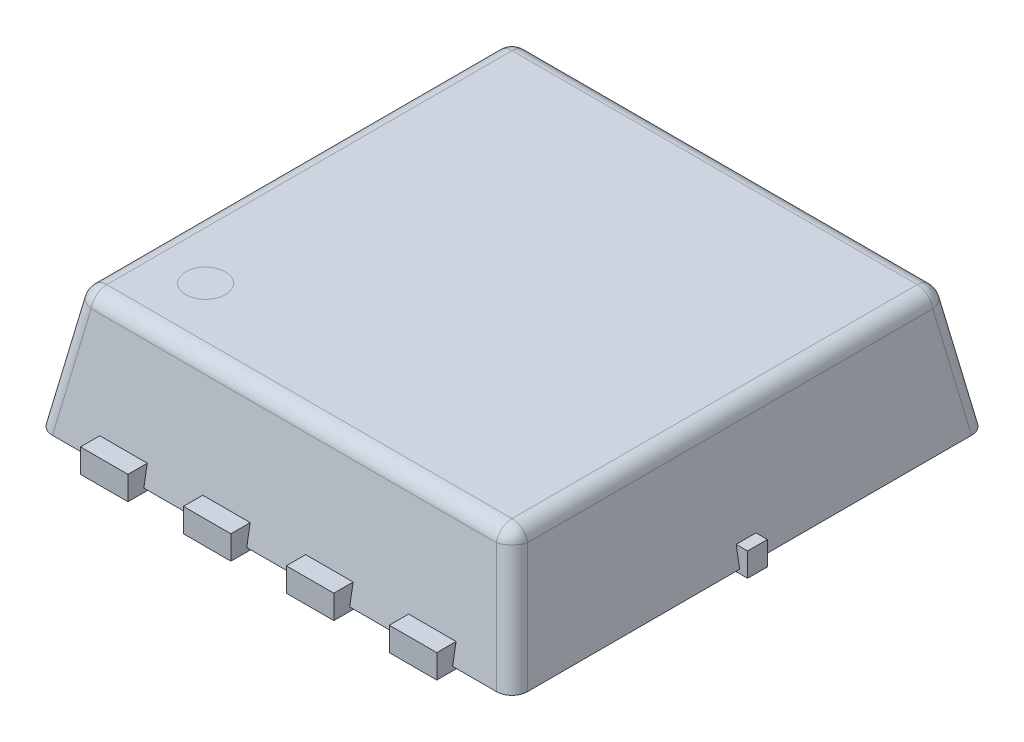
SolidWorks part; units mm, degrees
note: The reader was unsure of these and kept them because the rebuilt part matched: shared geometry of "Эскиз2<2>", "Эскиз3<2>".
ref_plane "Спереди" through (0, 0, 0) normal (0, 0, 1) x (1, 0, 0)
ref_plane "Сверху" through (0, 0, 0) normal (0, 1, 0) x (1, 0, 0)
ref_plane "Справа" through (0, 0, 0) normal (1, 0, 0) x (0, 0, -1)
sketch "Эскиз1" plane through (0, 0, 0) normal (0, 1, 0) x (1, 0, 0)
  line L1 (-1.5, -1.5) -> (1.5, -1.5)
  line L2 (-1.5, -1.5) -> (-1.5, 1.5)
  line L3 (-1.5, 1.5) -> (1.5, 1.5)
  line L4 (1.5, -1.5) -> (1.5, 1.5)
  line L5 (-1.5, -1.5) -> (1.5, 1.5) construction
  line L6 (-1.5, 1.5) -> (1.5, -1.5) construction
  point P0 (0, 0)
  dimension "D1" = 3
  dimension "D2" = 3
extrude "Бобышка-Вытянуть1" add sketch "Эскиз1" along normal blind 0.775 draft 10 from offset 0.025
fillet "Скругление1" radius 0.1 8 edges at (1.4317, 0.4125, -1.4317) (-1.4317, 0.4125, -1.4317) (-1.3633, 0.8, 0) (0, 0.8, -1.3633) (1.3633, 0.8, 0) (1.4317, 0.4125, 1.4317) (0, 0.8, 1.3633) (-1.4317, 0.4125, 1.4317)
sketch "Эскиз2" plane through (0, 0, 0) normal (0, 1, 0) x (1, 0, 0)
  line L0 (0, 0) -> (0, -1.5) construction
  line L1 (-0.975, 1.8089) -> (-0.975, -1.8739) construction
  line L2 (-0.475, -1.6) -> (-0.175, -1.6)
  line L3 (-1.125, -1.2) -> (-0.825, -1.2)
  line L4 (-1.125, -1.2) -> (-1.125, -1.6)
  line L5 (-1.125, -1.6) -> (-0.825, -1.6)
  line L6 (-0.825, -1.2) -> (-0.825, -1.6)
  line L7 (-1.125, -1.2) -> (-0.825, -1.6) construction
  line L8 (-1.125, -1.6) -> (-0.825, -1.2) construction
  line L9 (-0.475, -1.2) -> (-0.475, -1.6)
  line L10 (-0.475, -1.2) -> (-0.175, -1.2)
  line L11 (-0.175, -1.2) -> (-0.175, -1.6)
  line L12 (0.175, -1.6) -> (0.475, -1.6)
  line L13 (0.175, -1.2) -> (0.175, -1.6)
  line L14 (0.175, -1.2) -> (0.475, -1.2)
  line L15 (0.475, -1.2) -> (0.475, -1.6)
  line L16 (0.825, -1.6) -> (1.125, -1.6)
  line L17 (0.825, -1.2) -> (0.825, -1.6)
  line L18 (0.825, -1.2) -> (1.125, -1.2)
  line L19 (1.125, -1.2) -> (1.125, -1.6)
  line L20 (-0.825, -1.6) -> (1.125, -1.6) construction
  line L21 (-1.4015, -1.5) -> (1.4015, -1.5) construction
  line L22 (-0.175, 1.3) -> (-0.175, 1.6)
  line L23 (-1.125, 1.3) -> (-0.825, 1.3) construction
  line L24 (-1.125, 1.3) -> (-1.125, 1.6)
  line L25 (-1.125, 1.6) -> (-0.825, 1.6)
  line L26 (-0.825, 1.3) -> (-0.825, 1.6)
  line L27 (-1.125, 1.3) -> (-0.825, 1.6) construction
  line L28 (-1.125, 1.6) -> (-0.825, 1.3) construction
  line L29 (-0.475, 1.3) -> (-0.475, 1.6)
  line L30 (-0.475, 1.6) -> (-0.175, 1.6)
  line L31 (0.475, 1.3) -> (0.475, 1.6)
  line L32 (0.175, 1.3) -> (0.175, 1.6)
  line L33 (0.175, 1.6) -> (0.475, 1.6)
  line L34 (1.125, 1.3) -> (1.125, 1.6)
  line L35 (0.825, 1.3) -> (0.825, 1.6)
  line L36 (0.825, 1.6) -> (1.125, 1.6)
  line L37 (-0.825, 1.6) -> (1.125, 1.6) construction
  line L38 (-1.175, 1.3) -> (-1.175, 1.17)
  line L39 (-1.125, 1.3) -> (-1.175, 1.3) construction
  line L40 (-0.775, 1.3) -> (-0.775, 1.17)
  line L41 (-1.175, 1.3) -> (-1.125, 1.3)
  line L42 (-0.825, 1.3) -> (-0.775, 1.3)
  line L43 (-0.525, 1.3) -> (-0.525, 1.17)
  line L44 (-0.525, 1.3) -> (-0.475, 1.3)
  line L45 (-0.175, 1.3) -> (-0.125, 1.3)
  line L46 (-0.125, 1.3) -> (-0.125, 1.17)
  line L47 (0.125, 1.3) -> (0.125, 1.17)
  line L48 (0.125, 1.3) -> (0.175, 1.3)
  line L49 (0.475, 1.3) -> (0.525, 1.3)
  line L50 (0.525, 1.3) -> (0.525, 1.17)
  line L51 (0.775, 1.3) -> (0.775, 1.17)
  line L52 (0.775, 1.3) -> (0.825, 1.3)
  line L53 (1.125, 1.3) -> (1.175, 1.3)
  line L54 (1.175, 1.3) -> (1.175, 1.17)
  line L55 (-0.775, 1.17) -> (-0.525, 1.17)
  line L56 (-0.125, 1.17) -> (0.125, 1.17)
  line L57 (0.525, 1.17) -> (0.775, 1.17)
  line L58 (1.175, 1.17) -> (1.175, 0.165)
  line L59 (1.175, -0.58) -> (-1.175, -0.58)
  line L60 (-1.175, -0.58) -> (-1.175, 1.17) construction
  line L61 (-2.3963, 0) -> (1.6777, 0) construction
  line L62 (1.175, -0.165) -> (1.175, -0.58)
  line L63 (1.3, -0.165) -> (1.175, -0.165)
  line L64 (1.3, -0.165) -> (1.3, -0.0625)
  line L65 (1.3, 0.165) -> (1.175, 0.165)
  line L66 (-1.3, 0.165) -> (-1.175, 0.165)
  line L67 (1.3, -0.165) -> (1.175, 0.165) construction
  line L68 (1.3, 0.165) -> (1.175, -0.165) construction
  line L69 (-1.3, -0.165) -> (-1.3, -0.0625)
  line L70 (-1.3, -0.165) -> (-1.175, -0.165)
  line L71 (-1.175, 1.17) -> (-1.175, 0.165)
  line L73 (-1.175, -0.58) -> (-1.175, -0.165)
  line L74 (1.3, 0.0625) -> (1.3, 0.165)
  line L75 (1.55, -0.0625) -> (1.3, -0.0625)
  line L76 (1.55, -0.0625) -> (1.55, 0.0625)
  line L77 (1.55, 0.0625) -> (1.3, 0.0625)
  line L78 (-1.55, -0.0625) -> (-1.55, 0.0625)
  line L79 (1.55, -0.0625) -> (1.3, 0.0625) construction
  line L80 (1.55, 0.0625) -> (1.3, -0.0625) construction
  line L81 (-1.55, -0.0625) -> (-1.3, -0.0625)
  line L82 (-1.55, 0.0625) -> (-1.3, 0.0625)
  line L83 (-1.3, 0.0625) -> (-1.3, 0.165)
  point P5 (-0.975, -1.4)
  point P10 (-0.975, 1.45)
  point P53 (1.2375, 0)
  point P70 (1.425, 0)
  dimension "D1" = 0.975
  dimension "D2" = 1.6
  dimension "D3" = 0.3
  dimension "D4" = 0.4
  dimension "D6" = 0.65
  dimension "D7" = 0.3
  dimension "D8" = 0.3
  dimension "D9" = 1.6
  dimension "D10" = 3.2
  dimension "D12" = 0.65
  dimension "D13" = 0.2
  dimension "D14" = 0.43
  dimension "D15" = 1.75
  dimension "D16" = 0.58
  dimension "D17" = 0.33
  dimension "D18" = 1.3
  dimension "D19" = 0.125
  dimension "D20" = 1.55
  dimension "D5" = 4
  dimension "D11" = 4
  dimension "D21" = 4
extrude "Вырез-Вытянуть1" cut sketch "Эскиз2" along normal blind 0.15
extrude "Бобышка-Вытянуть2" add sketch "Эскиз2<2>" along normal blind 0.15 separate body
sketch "Эскиз2<2>" plane through (0, 0, 0) normal (0, 1, 0) x (1, 0, 0) same geometry as "Эскиз2"
sketch "Эскиз3" plane through (0, 0, 0) normal (0, 1, 0) x (1, 0, 0)
  line L0 (-0.975, 0.6956) -> (-0.975, -1.6) construction
  line L2 (-1.8162, -0.96) -> (0.4033, -0.96) construction
  line L3 (-1.4015, -1.5) -> (-1.125, -1.5) construction
  line L4 (-1.125, -1.6) -> (-0.825, -1.6) construction
  line L5 (-1.5, -0.0625) -> (-1.5, -1.4015) construction
  circle A0 centre (-0.975, -0.96) radius 0.125
  point P8 (-0.975, -0.96)
  dimension "D3" = 0.25
  dimension "D1" = 0.525
  dimension "D2" = 0.54
extrude "Вырез-Вытянуть2" cut sketch "Эскиз3" against normal blind 0.05 from offset 0.8
extrude "Бобышка-Вытянуть3" add sketch "Эскиз3<2>" against normal blind 0.05 from offset 0.8 separate body
sketch "Эскиз3<2>" plane through (0, 0, 0) normal (0, 1, 0) x (1, 0, 0) same geometry as "Эскиз3"
